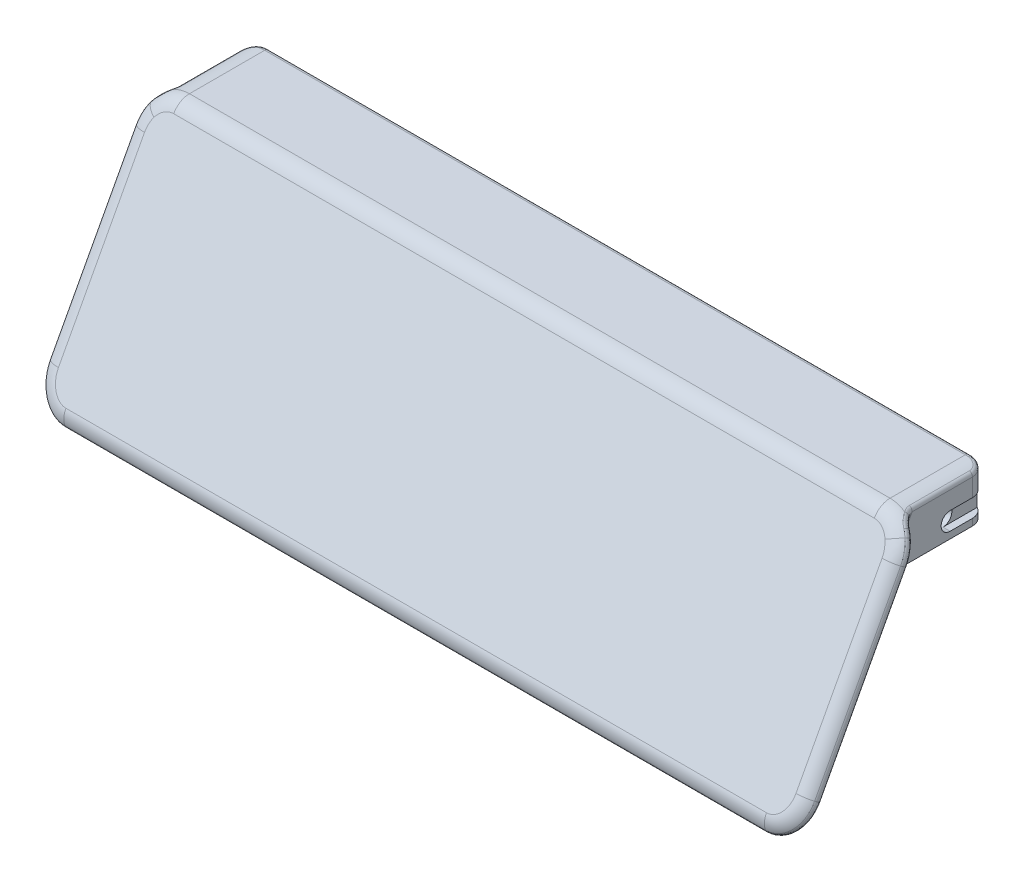
SolidWorks part; units mm, degrees
ref_plane "Front Plane" through (0, 0, 0) normal (0, 0, 1) x (1, 0, 0)
ref_plane "Top Plane" through (0, 0, 0) normal (0, 1, 0) x (1, 0, 0)
ref_plane "Right Plane" through (0, 0, 0) normal (1, 0, 0) x (0, 0, -1)
sketch "Sketch1" plane through (0, 0, 0) normal (1, 0, 0) x (0, 0, -1)
  line L0 (0, 0) -> (-5, 0)
  line L1 (-5, 0) -> (-18.0985, -24.449)
  line L2 (0, 1.5) -> (-5.8981, 1.5)
  line L3 (-5.8981, 1.5) -> (-19.8002, -24.449)
  line L4 (0, 0) -> (0, 1.5)
  line L5 (-18.0985, -24.449) -> (-19.8002, -24.449)
  line L6 (-5.8981, 1.5) -> (-19.4207, -23.7406) construction
  line L7 (-5, 0) -> (-18.0985, -24.449) construction
  dimension "D2" = 118.18
  dimension "D1" = 5
  dimension "D3" = 24.449
  dimension "D4" = 1.5
extrude "Boss-Extrude1" add sketch "Sketch1" along normal mid plane 86.28
sketch "Sketch2" plane through (0, 1.5, 0) normal (0, 1, 0) x (1, 0, 0)
  line L0 (-43.14, 0) -> (-43.14, -5.8981) construction
  line L1 (-43.14, 0) -> (-40.94, 0)
  line L2 (-43.14, 0) -> (-43.14, -5.8981)
  line L3 (-43.14, -5.8981) -> (-40.94, -5.8981)
  line L4 (-40.94, 0) -> (-40.94, -5.8981)
  line L5 (43.14, 0) -> (-43.14, 0) construction
  line L6 (43.14, -5.8981) -> (-43.14, -5.8981) construction
  line L7 (-41.14, -3.4737) -> (-41.14, 0.2897) construction
  dimension "D1" = 0.2
extrude "Cut-Extrude1" cut sketch "Sketch2" against normal through all
sketch "Sketch3" plane through (0, 0, 0) normal (0, 0, -1) x (-1, 0, 0)
  line L0 (40.94, -1.6763) -> (40.94, 1.5) construction
  line L1 (-43.14, 0) -> (40.94, 0)
  line L2 (-43.14, 0) -> (-43.14, -4)
  line L3 (-43.14, -4) -> (40.94, -4)
  line L4 (40.94, 0) -> (40.94, -4)
  dimension "D1" = 4
extrude "Boss-Extrude2" add sketch "Sketch3" against normal up to next
sketch "Sketch4" plane through (-40.94, 0, 0) normal (-1, 0, 0) x (0, 0, 1)
  line L0 (5.8981, -1.6763) -> (7.143, -4) construction
  line L1 (5.8981, -1.6763) -> (7.143, -4)
  line L2 (5.8981, -1.6763) -> (5.8981, 1.5) construction
  line L5 (5.8981, -1.6763) -> (5.8981, 1.5)
  line L7 (5.8981, 1.5) -> (19.8002, -24.449) construction
  line L8 (7.143, -4) -> (7.143, -0.8237)
  line L9 (5.8981, 1.5) -> (7.143, -0.8237)
extrude "Boss-Extrude3" add sketch "Sketch4" along normal up to surface (2.2 mm away) up to face at (-43.14, -12.2686, 12.4237)
sketch "Sketch5" plane through (-43.14, 0, 0) normal (-1, 0, 0) x (0, 0, 1)
  line L1 (5.8981, -1.6763) -> (4.1964, 1.5)
  line L4 (5.8981, 1.5) -> (0, 1.5) construction
  line L5 (4.1964, 1.5) -> (5.8981, 1.5)
  line L7 (5.8981, 1.5) -> (5.8981, -1.6763)
  line L8 (18.0985, -24.449) -> (5.8981, -1.6763) construction
  line L9 (5.8981, 1.5) -> (19.8002, -24.449) construction
  line L10 (5.8981, -1.6763) -> (5.8981, 1.5) construction
extrude "Boss-Extrude4" add sketch "Sketch5" against normal up to surface (2.2 mm away) up to face at (-40.94, -1.3353, 3.7878)
sketch "Sketch11" plane through (0, 0, 0) normal (0, 0, -1) x (-1, 0, 0)
  line L4 (-43.14, 1.5) -> (-43.14, -4)
  line L5 (-43.14, -4) -> (40.94, -4)
  line L6 (40.94, -4) -> (40.94, 1.5)
  line L7 (40.94, 1.5) -> (-43.14, 1.5)
  line L8 (-43.14, 1.5) -> (-43.14, -4)
  line L9 (-43.14, -4) -> (40.94, -4)
  line L10 (40.94, -4) -> (40.94, 1.5)
  line L11 (40.94, 1.5) -> (-43.14, 1.5)
  dimension "D1" = 0
extrude "Boss-Extrude7" add sketch "Sketch11" along normal blind 4.2
sketch "Sketch6" plane through (-40.94, 0, 0) normal (-1, 0, 0) x (0, 0, 1)
  line L0 (-4.2, -2.25) -> (-0.2, -2.25) construction
  line L2 (-4.2, -4) -> (-4.2, 1.5) construction
  line L3 (-4.2, -1.25) -> (2.7569, -1.25) construction
  circle A0 centre (-0.2, -2.25) radius 1
  dimension "D1" = 2
  dimension "D2" = 4
  dimension "D3" = 1
sketch "Sketch7" plane through (43.14, 0, 0) normal (1, 0, 0) x (0, 0, -1)
  line L4 (-4.1964, 1.5) -> (-7.143, -4)
  line L5 (4.2, 1.5) -> (-4.1964, 1.5)
  line L6 (4.2, -4) -> (4.2, 1.5)
  line L7 (-7.143, -4) -> (4.2, -4)
  line L8 (-4.1964, 1.5) -> (-7.143, -4)
  line L9 (4.2, 1.5) -> (-4.1964, 1.5)
  line L10 (4.2, -4) -> (4.2, 1.5)
  line L11 (-7.143, -4) -> (4.2, -4)
  dimension "D1" = 0
extrude "Cut-Extrude2" cut sketch "Sketch7" against normal blind 2.2
sketch "Sketch8" plane through (40.94, 0, 0) normal (1, 0, 0) x (0, 0, -1)
  circle A0 centre (0.2, -2.25) radius 1 construction
  circle A1 centre (0.2, -2.25) radius 1
fillet "Fillet10" radius 1.5 2 edges at (40.94, -1.25, -4.2) (-40.94, -1.25, -4.2)
fillet "Fillet9" radius 4 2 edges at (43.14, -24.449, 18.9493) (-43.14, -24.449, 18.9493)
fillet "Fillet3" radius 0.5 2 edges at (40.94, -1.25, 5.6697) (-40.94, -1.25, 5.6697)
fillet "Fillet4" radius 1 1 edges at (0, -4, 7.143)
fillet "Fillet12" radius 4 2 edges at (-43.14, 1.5, 5.0472) (43.14, 1.5, 5.0472)
fillet "Fillet5" radius 2 3 edges at (0, 1.5, 5.8981) (41.9684, 0.3284, 6.5258) (-41.9684, 0.3284, 6.5258)
fillet "Fillet11" radius 0.5 15 edges at (-43.14, -11.4745, 11.1474) (-42.9854, -1.3987, 5.7493) (-42.0448, 0.25, 4.8661) (-41.0734, 1.0017, 4.2818) (-40.94, 1.0721, 0.5792) (-40.6563, 1.2015, -3.5779) (-39.2901, 1.4972, -4.2) (0, 1.5, -4.2) (39.2901, 1.4972, -4.2) (40.3489, 1.3129, -3.8933) (40.94, 1.0721, 0.5792) (41.0841, 0.9958, 4.2977) (42.0448, 0.25, 4.8661) (42.9854, -1.3987, 5.7493) (43.14, -11.4745, 11.1474)
extrude "Cut-Extrude3" cut sketch "Sketch6" against normal through all
sketch "Sketch12" plane through (-40.94, 0, 0) normal (-1, 0, 0) x (0, 0, 1)
  line L0 (-4.2, -4) -> (-4.2, 0.9871) construction
  line L1 (-0.2, -1.25) -> (-4.2, -1.25)
  line L2 (-0.2, -3.25) -> (-4.2, -3.25)
  line L3 (-4.2, -1.25) -> (-4.2, -3.25)
  circle A2 centre (-0.2, -2.25) radius 1 construction
  arc A3 (-0.2, -3.25) -> (-0.2, -1.25) centre (-0.2, -2.25) ccw
extrude "Cut-Extrude4" cut sketch "Sketch12" against normal blind 0.8
sketch "Sketch13" plane through (40.94, 0, 0) normal (1, 0, 0) x (0, 0, -1)
  line L0 (0.2, -1.25) -> (4.2, -1.25) construction
  line L1 (4.2, -1.25) -> (4.2, -3.25) construction
  line L2 (0.2, -3.25) -> (4.2, -3.25) construction
  line L3 (0.2, -1.25) -> (4.2, -1.25)
  line L8 (4.2, -1.25) -> (4.2, -3.25)
  line L9 (0.2, -3.25) -> (4.2, -3.25)
  arc A0 (0.2, -1.25) -> (0.2, -3.25) centre (0.2, -2.25) ccw construction
  arc A2 (0.2, -1.25) -> (0.2, -3.25) centre (0.2, -2.25) ccw
extrude "Cut-Extrude5" cut sketch "Sketch13" against normal blind 0.8
sketch "Sketch14" plane through (0, 0, -4.2) normal (0, 0, -1) x (-1, 0, 0)
  line L0 (41.44, -4.5278) -> (-41.44, -4.5278) construction
  line L1 (-38.94, -4.5278) -> (38.94, -4.5278)
  line L2 (-38.94, -4.5278) -> (-38.94, -0.5)
  line L3 (-38.94, -0.5) -> (38.94, -0.5)
  line L4 (38.94, -4.5278) -> (38.94, -0.5)
  line L5 (0, -0.5) -> (0, 13.0688) construction
  line L7 (-40.94, 0.7496) -> (-40.94, -4.0005) construction
  line L8 (-39.14, 1.5) -> (39.14, 1.5) construction
  dimension "D1" = 2
  dimension "D2" = 2
extrude "Cut-Extrude6" cut sketch "Sketch14" against normal up to surface (11.6257 mm away) up to face at (0.0299, -8.8456, 9.739)
